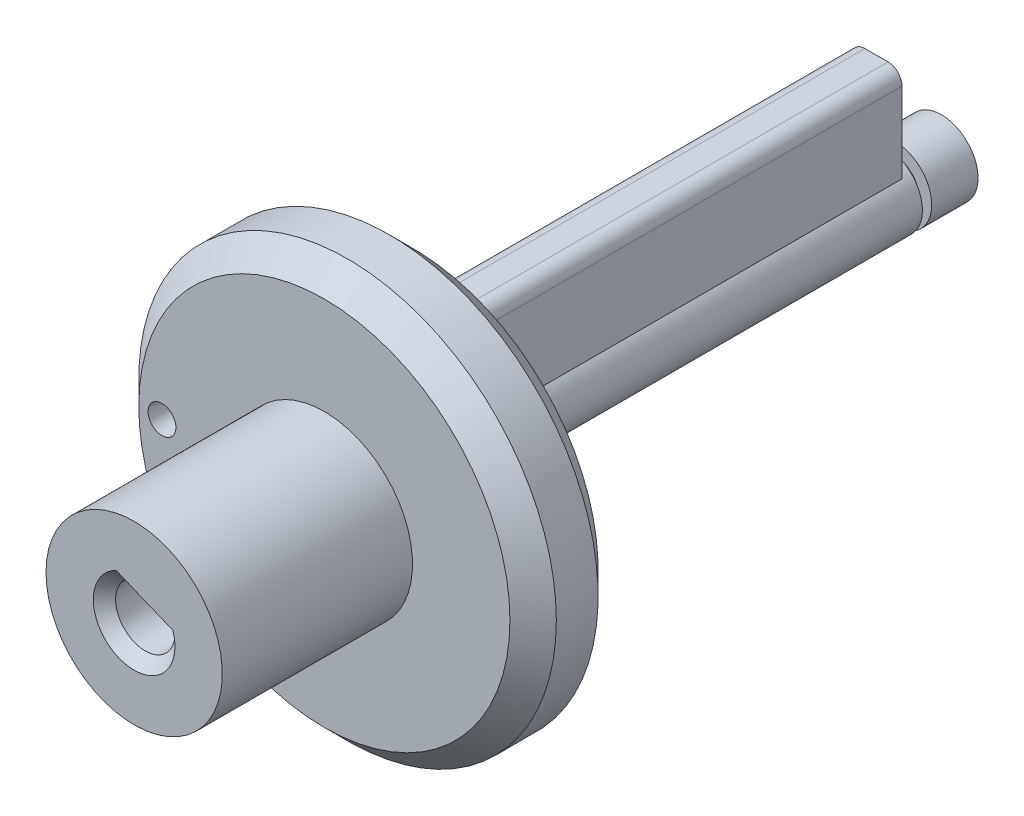
SolidWorks part; units mm, degrees
material "Zinc AG40A (Zn-4Al-0.4Mg; Zamak 3), Cast"
ref_plane "Front Plane" through (0, 0, 0) normal (0, 0, 1) x (1, 0, 0)
ref_plane "Top Plane" through (0, 0, 0) normal (0, 1, 0) x (1, 0, 0)
ref_plane "Right Plane" through (0, 0, 0) normal (1, 0, 0) x (0, 0, -1)
sketch "Sketch1" plane through (0, 0, 0) normal (0, 0, 1) x (1, 0, 0)
  line L0 (-1.2429, 3.556) -> (-1.8135, 0.3198)
  line L1 (-1.2429, 3.556) -> (1.2429, 3.556)
  line L2 (1.2429, 3.556) -> (1.8135, 0.3198)
  line L3 (0, 3.3051) -> (0, 0) construction
  arc A0 (-1.8135, 0.3198) -> (1.8135, 0.3198) centre (0, 0) ccw
  dimension "D1" = 3.683
  dimension "D2" = 10
  dimension "D3" = 10
  dimension "D4" = 3.556
extrude "Extrude1" add sketch "Sketch1" along normal blind 0.0003
sketch "Sketch8" plane through (0, 0, 0.0003) normal (0, 0, 1) x (1, 0, 0)
  circle A2 centre (0, 0) radius 2.413
  dimension "D1" = 4.826
extrude "Extrude8" add sketch "Sketch8" along normal blind 7.62
sketch "Sketch6" plane through (0, 0, 0.0003) normal (0, 0, 1) x (1, 0, 0)
  circle A0 centre (0, 0) radius 5.715
  dimension "D1" = 11.43
extrude "Extrude6" add sketch "Sketch6" along normal blind 2.413
sketch "Sketch4" plane through (0, 0, 7.6203) normal (0, 0, 1) x (1, 0, 0)
  circle A0 centre (0, 0) radius 0.254
  dimension "D1" = 0.508
extrude "Extrude4" cut sketch "Sketch4" against normal blind 6.731
sketch "Sketch5" plane through (0, 0, 0) normal (0, 0, -1) x (-1, 0, 0)
  circle A0 centre (0, 0) radius 1.0033
  dimension "D1" = 2.0066
extrude "Extrude5" add sketch "Sketch5" along normal blind 12.954
fillet "Fillet2" radius 0.889 2 edges at (-1.2429, 3.556, 0.0001) (1.2429, 3.556, 0.0001)
chamfer "Chamfer1" distance 0.635 angle 45 1 edges at (5.715, 0, 0.0003)
chamfer "Chamfer3" distance 0.635 angle 45 1 edges at (5.715, 0, 2.4133)
sketch "Sketch9" plane through (0, 0, 0) normal (0, 0, -1) x (-1, 0, 0)
  line L1 (-0.3175, 3.302) -> (0.3175, 3.302)
  line L2 (-0.6985, 2.921) -> (-0.6985, 0)
  line L3 (-0.6985, 0) -> (0.6985, 0)
  line L4 (0.6985, 2.921) -> (0.6985, 0)
  arc A0 (-0.3175, 3.302) -> (-0.6985, 2.921) centre (-0.3175, 2.921) ccw
  arc A1 (0.3175, 3.302) -> (0.6985, 2.921) centre (0.3175, 2.921) cw
  point P4 (0, 0)
  dimension "D3" = 0.381
  dimension "D1" = 1.397
  dimension "D2" = 3.302
extrude "Extrude9" add sketch "Sketch9" along normal blind 12.7
sketch "Sketch17" plane through (0, 0, 7.6203) normal (0, 0, 1) x (1, 0, 0)
  line L0 (0, 0) -> (0.4411, 1.0649) construction
  line L2 (0, 0) -> (0, 0.8128)
  line L4 (0, 0) -> (0.5747, 0.5747)
  circle A0 centre (0, 0) radius 0.7366 construction
  arc A1 (0.1537, 0.7981) -> (0.4557, 0.673) centre (0.3791, 0.9152) ccw
  arc A3 (0.5747, 0.5747) -> (0.4557, 0.673) centre (0, 0) ccw
  arc A4 (0.1537, 0.7981) -> (0, 0.8128) centre (0, 0) ccw
  dimension "D2" = 45
  dimension "D3" = 22.5
  dimension "D4" = 1.4732
  dimension "D1" = 0.508
  dimension "D6" = 1.6256
extrude "Extrude11" cut sketch "Sketch17" against normal blind 6.731
pattern_circular "CirPattern1" count 8 over 360 about axis through (0, 0, 7.6203) along (0, 0, 1) of "Extrude11"
sketch "Sketch18" plane through (0, 0, 7.6203) normal (0, 0, 1) x (1, 0, 0)
  line L0 (0, 0) -> (-0.3475, 0) construction
  line L1 (-0.5392, 0.6082) -> (0.8113, 0.0488)
  line L2 (-0.5392, 0.6082) -> (-0.3642, 1.0306)
  line L3 (-0.3642, 1.0306) -> (0.9863, 0.4712)
  line L4 (0.8113, 0.0488) -> (0.9863, 0.4712)
  arc A0 (-0.4557, 0.673) -> (-0.673, 0.4557) centre (0, 0) ccw construction
  arc A1 (0.673, 0.4557) -> (0.4557, 0.673) centre (0, 0) ccw construction
  arc A2 (0.7981, -0.1537) -> (0.7981, 0.1537) centre (0, 0) ccw construction
  arc A3 (-0.4599, 0.5754) -> (0.7321, 0.0817) centre (0, 0) cw construction
  arc A4 (0.1537, 0.7981) -> (0.4557, 0.673) centre (0.3791, 0.9152) ccw construction
  dimension "D1" = 0.381
  dimension "D2" = 22.5
extrude "Extrude12" add sketch "Sketch18" against normal up to surface (6.731 mm away) up to face at (0, 0, 0.8893)
chamfer "Chamfer4" distance 0.381 angle 60 1 edges at (0.1361, 0.3285, 7.6203) first distance on face at (-0.0964, -0.2328, 7.6203)
sketch "Sketch19" plane through (0, 0, 7.6203) normal (0, 0, 1) x (1, 0, 0)
  line L0 (0.8113, 0.0488) -> (-0.5392, 0.6082) construction
  line L1 (0.8113, 0.0488) -> (-0.5392, 0.6082)
  arc A0 (-0.7981, 0.1537) -> (-0.7981, -0.1537) centre (0, 0) ccw construction
  arc A1 (-0.5392, 0.6082) -> (0.8113, 0.0488) centre (0, 0) ccw
extrude "Extrude13" cut sketch "Sketch19" against normal blind 0.6604
sketch "Sketch20" plane through (0, 0, 0) normal (1, 0, 0) x (0, 0, -1)
  line L0 (-6.9599, -0.8128) -> (-6.9599, 0)
  line L1 (-6.9599, 0) -> (-6.1471, 0)
  line L2 (-6.1471, 0) -> (-6.9599, -0.8128)
  line L5 (-6.9599, -0.6612) -> (-6.9599, -0.7981) construction
  line L6 (-7.3896, 0) -> (-5.2833, 0) construction
  line L7 (-6.9599, -0.673) -> (-6.9599, -0.7981) construction
  dimension "D1" = 0.8128
  dimension "D2" = 45
revolve "Cut-Revolve1" cut sketch "Sketch20" angle 130 about L6 other way angle 90
ref_plane "Plane1" through (0, 0, 6.9603) normal (0, 0, 1) x (1, 0, 0)
ref_plane "Plane2" through (0, 0, 6.9603) normal (0, 0, 1) x (1, 0, 0)
sketch "Sketch21" plane through (0, 0, 6.9603) normal (0, 0, 1) x (1, 0, 0)
  line L0 (0.8113, 0.0488) -> (-0.5392, 0.6082) construction
  line L1 (-0.4599, 0.5754) -> (-0.5392, 0.6082)
  line L2 (0.7321, 0.0817) -> (0.8113, 0.0488)
  arc A0 (0.7321, 0.0817) -> (-0.4599, 0.5754) centre (0, 0) cw
  arc A1 (0.8113, 0.0488) -> (-0.5392, 0.6082) centre (0, 0) cw
  arc A2 (-0.0356, 0.812) -> (0.5993, 0.549) centre (0, 0) ccw construction
  dimension "D1" = 0.7366
extrude "Boss-Extrude1" add sketch "Sketch21" against normal up to surface (6.0711 mm away) up to face at (-0.0964, -0.2328, 0.8893)
sketch "Sketch22" plane through (0, 0, 6.9603) normal (0, 0, 1) x (1, 0, 0)
  line L2 (-0.4599, 0.5754) -> (-0.5392, 0.6082)
  line L3 (0.8113, 0.0488) -> (0.7321, 0.0817)
  line L4 (-0.4599, 0.5754) -> (-0.5392, 0.6082)
  line L5 (0.8113, 0.0488) -> (0.7321, 0.0817)
  arc A2 (-0.4599, 0.5754) -> (0.7321, 0.0817) centre (0, 0) ccw
  arc A3 (-0.5392, 0.6082) -> (0.8113, 0.0488) centre (0, 0) ccw
  arc A4 (-0.4599, 0.5754) -> (0.7321, 0.0817) centre (0, 0) ccw
  arc A5 (-0.5392, 0.6082) -> (0.8113, 0.0488) centre (0, 0) ccw
  dimension "D1" = 0
extrude "Cut-Extrude1" cut sketch "Sketch22" against normal offset from surface (0.8387 mm away) 1.4986 up to face at (-0.0146, -0.0352, 7.6203)
chamfer "Chamfer5" distance 0.1016 angle 45 1 edges at (-0.2819, -0.6805, 6.1217)
chamfer "Chamfer6" distance 0.3048 angle 45 1 edges at (-0.311, -0.7509, 7.6203)
sketch "Sketch27" plane through (0, 0, 0) normal (0, 0, 1) x (1, 0, 0)
  circle A0 centre (-4.445, 0) radius 0.381
extrude "Cut-Extrude5" cut sketch "Sketch27" along normal through all
sketch "Sketch28" plane through (0, 0, 0.0003) normal (0, 0, -1) x (-1, 0, 0)
  line L0 (4.445, 1.0147) -> (6.1908, 1.4132)
  line L1 (4.445, -1.0147) -> (6.1908, -1.4132)
  arc A0 (4.445, 1.0147) -> (4.445, -1.0147) centre (4.445, 0) ccw
  arc A3 (6.1908, -1.4132) -> (6.1908, 1.4132) centre (0, 0) ccw
extrude "Cut-Extrude7" cut sketch "Sketch28" against normal blind 1.27 contours L0 A3 L1 A0
sketch "Sketch29" plane through (0, 0, -12.954) normal (0, 0, -1) x (-1, 0, 0)
  circle A0 centre (0, 0) radius 0.6604
extrude "Boss-Extrude2" add sketch "Sketch29" along normal blind 1.524
sketch "Sketch30" plane through (0, 0, -14.478) normal (0, 0, -1) x (-1, 0, 0)
  circle A0 centre (0, 0) radius 1.0033
extrude "Boss-Extrude3" add sketch "Sketch30" against normal blind 1.27
